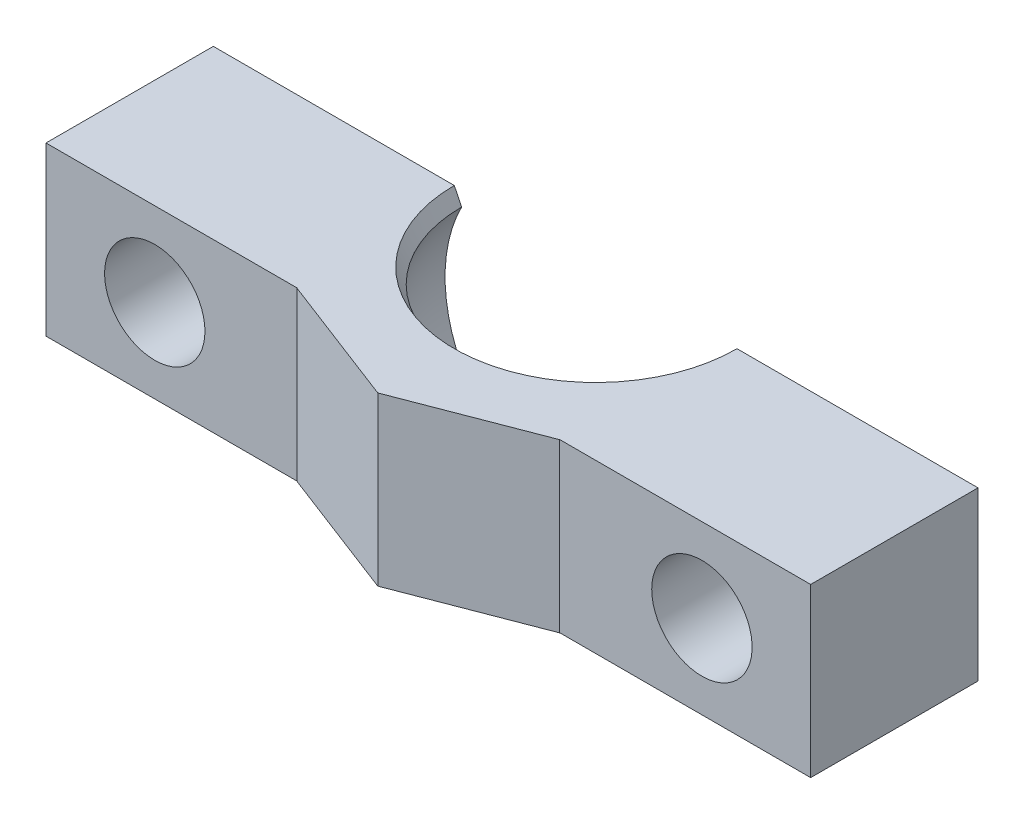
SolidWorks part; units mm, degrees
ref_plane "Front Plane" through (0, 0, 0) normal (0, 0, 1) x (1, 0, 0)
ref_plane "Top Plane" through (0, 0, 0) normal (0, 1, 0) x (1, 0, 0)
ref_plane "Right Plane" through (0, 0, 0) normal (1, 0, 0) x (0, 0, -1)
sketch "Sketch2" plane through (0, 0, 0) normal (0, 1, 0) x (1, 0, 0)
  line L1 (0, 0) -> (-45.7, 0)
  line L2 (0, 0) -> (0, -15)
  line L3 (0, -15) -> (-45.7, -15)
  line L4 (-45.7, 0) -> (-45.7, -15)
  dimension "D1" = 45.7
  dimension "D2" = 15
extrude "Boss-Extrude1" add sketch "Sketch2" along normal blind 10
sketch "Sketch3" plane through (0, 0, 0) normal (0, 0, -1) x (-1, 0, 0)
  line L0 (0, 10) -> (0, 0) construction
  line L1 (0, 10) -> (45.7, 10) construction
  line L2 (22.85, 14) -> (22.85, -4)
  line L3 (45.7, 10) -> (45.7, 0) construction
  arc A0 (22.85, 14) -> (22.85, -4) centre (22.85, 5) ccw
  dimension "D1" = 18
  dimension "D2" = 22.85
  dimension "D3" = 5
  dimension "D4" = 22.85
revolve "Cut-Revolve1" cut sketch "Sketch3" angle 360 about L2
sketch "Sketch4" plane through (0, 0, 0) normal (0, 0, -1) x (-1, 0, 0)
  line L0 (0, 0) -> (15.3667, 0) construction
  line L1 (0, 10) -> (0, 0) construction
  line L2 (45.7, 10) -> (45.7, 0) construction
  circle A0 centre (6.5, 5) radius 3
  circle A1 centre (39.2, 5) radius 3
  point P10 (0, 0)
  dimension "D1" = 6
  dimension "D2" = 5
  dimension "D3" = 6.5
  dimension "D4" = 6.5
extrude "Cut-Extrude1" cut sketch "Sketch4" against normal through all
sketch "Sketch5" plane through (0, 0, 15) normal (0, 0, 1) x (1, 0, 0)
  line L0 (-45.7, 0) -> (0, 0) construction
  line L1 (-45.7, 10) -> (-30.7, 10)
  line L2 (-45.7, 10) -> (-45.7, 0)
  line L3 (-45.7, 0) -> (-30.7, 0)
  line L4 (-30.7, 10) -> (-30.7, 0)
  line L6 (0, 10) -> (-15, 10)
  line L7 (0, 10) -> (0, 0)
  line L8 (0, 0) -> (-15, 0)
  line L9 (-15, 10) -> (-15, 0)
  dimension "D1" = 15
extrude "Cut-Extrude2" cut sketch "Sketch5" against normal blind 5
chamfer "Chamfer1" distance 13 angle 21 2 edges at (-15, 5, 15) (-30.7, 5, 15) first distance on face at (-22.85, 5, 15)
chamfer "Chamfer2" distance 1 angle 60 2 edges at (-22.85, 0, 7.4833) (-22.85, 10, 7.4833) first distance on face at (-22.85, 5, 3.7417)
